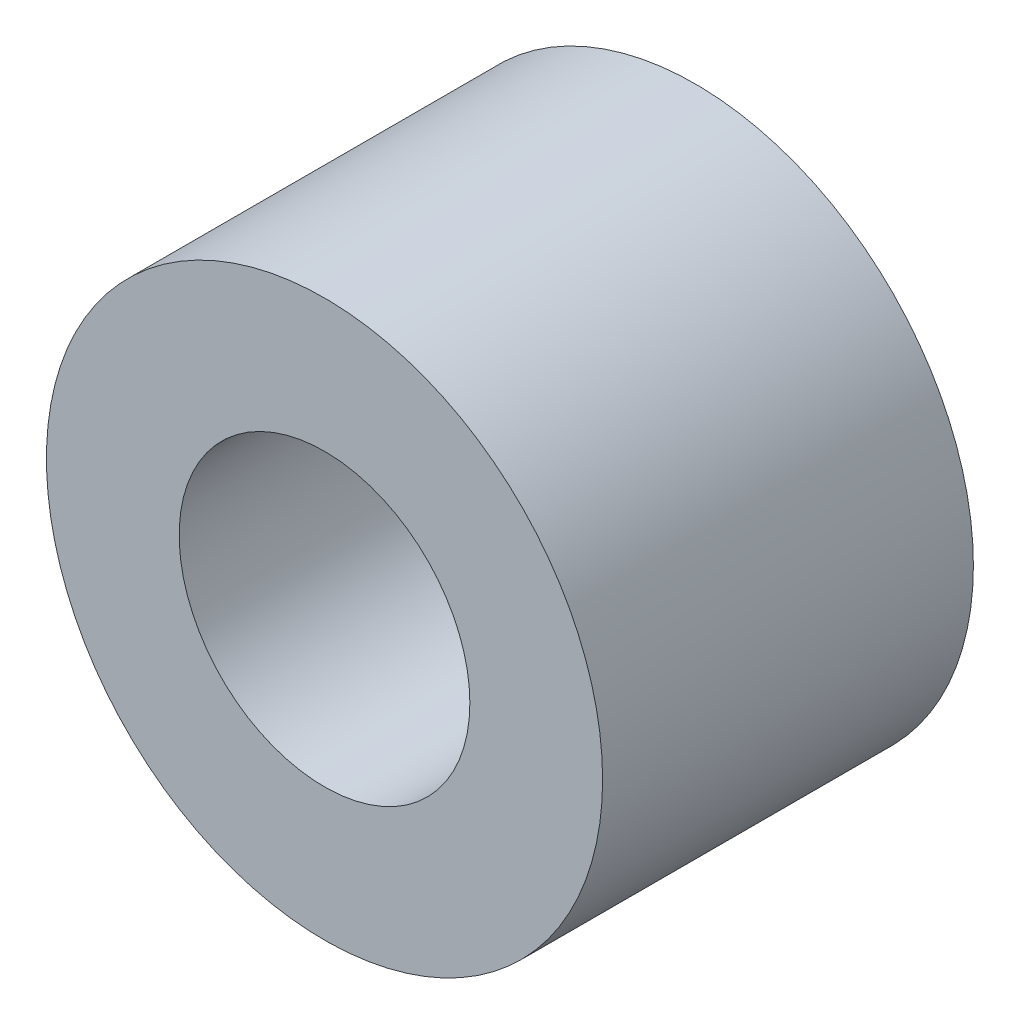
SolidWorks part; units mm, degrees
ref_plane "Front Plane" through (0, 0, 0) normal (0, 0, 1) x (1, 0, 0)
ref_plane "Top Plane" through (0, 0, 0) normal (0, 1, 0) x (1, 0, 0)
ref_plane "Right Plane" through (0, 0, 0) normal (1, 0, 0) x (0, 0, -1)
sketch "Sketch1" plane through (0, 0, 0) normal (0, 0, 1) x (1, 0, 0)
  circle A0 centre (0, 0) radius 4.7625
  circle A1 centre (0, 0) radius 2.4892
  dimension "D1" = 4.9784
  dimension "D2" = 9.525
extrude "Boss-Extrude1" add sketch "Sketch1" along normal blind 6.35
